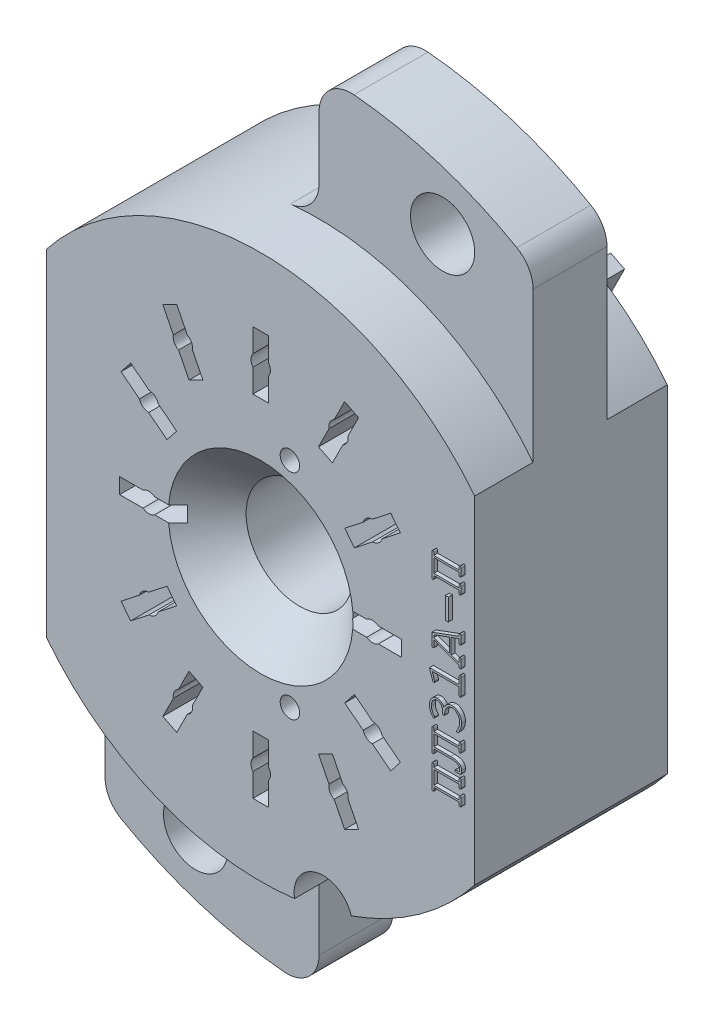
SolidWorks part; units mm, degrees
ref_plane "Front Plane" through (0, 0, 0) normal (0, 0, 1) x (1, 0, 0)
ref_plane "Top Plane" through (0, 0, 0) normal (0, 1, 0) x (1, 0, 0)
ref_plane "Right Plane" through (0, 0, 0) normal (1, 0, 0) x (0, 0, -1)
sketch "Sketch2" plane through (0, 0, 0) normal (0, 0, 1) x (1, 0, 0)
  line L0 (-31.5495, -8.6603) -> (-31.5495, -17.2988)
  line L2 (-31.5495, 8.6603) -> (-31.5495, -8.6603)
  line L4 (-9.5495, 8.6603) -> (-9.5495, -8.6603)
  line L5 (-20.5495, -20.5) -> (-20.5495, -14)
  line L6 (-9.5495, 8.6603) -> (-9.5495, 17.2988)
  line L7 (-20.5495, 14) -> (-20.5495, 20.5)
  arc A0 (-20.5495, -14) -> (-9.5495, -8.6603) centre (-20.5495, 0) ccw
  arc A1 (-20.5495, 14) -> (-31.5495, 8.6603) centre (-20.5495, 0) ccw
  arc A2 (-31.5495, -17.2988) -> (-20.5495, -20.5) centre (-20.5495, 0) ccw
  arc A4 (-9.5495, 17.2988) -> (-20.5495, 20.5) centre (-20.5495, 0) ccw
  arc A6 (-31.5495, -17.2988) -> (-20.5495, -20.5) centre (-20.5495, 0) ccw
  point P9 (-31.5495, -8.6603)
  point P10 (-31.5495, -17.2988)
  point P11 (-20.5495, -20.5)
  dimension "D1" = 28
  dimension "D3" = 41
  dimension "D6" = 11
  dimension "D2" = 22
  dimension "D4" = 17.3205
  dimension "D5" = 11
  dimension "D7" = 8.6386
extrude "Boss-Extrude1" add sketch "Sketch2" along normal blind 3.8 contours L6 A4 L7 A1 L2 L0 A2 L5 A0 L4 region at (-20.5495, 0, 0)
sketch "Sketch3" plane through (0, 0, 0) normal (0, 0, 1) x (1, 0, 0)
  line L0 (-31.5495, -8.6603) -> (-31.5495, -17.2988)
  line L2 (-31.5495, 8.6603) -> (-31.5495, -8.6603)
  line L4 (-9.5495, 8.6603) -> (-9.5495, -8.6603)
  line L5 (-20.5495, -20.5) -> (-20.5495, -14)
  line L6 (-9.5495, 8.6603) -> (-9.5495, 17.2988)
  line L7 (-20.5495, 14) -> (-20.5495, 20.5)
  arc A0 (-20.5495, -14) -> (-9.5495, -8.6603) centre (-20.5495, 0) ccw
  arc A1 (-20.5495, 14) -> (-31.5495, 8.6603) centre (-20.5495, 0) ccw
  arc A2 (-31.5495, -17.2988) -> (-20.5495, -20.5) centre (-20.5495, 0) ccw
  arc A4 (-9.5495, 17.2988) -> (-20.5495, 20.5) centre (-20.5495, 0) ccw
  arc A6 (-31.5495, -17.2988) -> (-20.5495, -20.5) centre (-20.5495, 0) ccw
  point P9 (-31.5495, -8.6603)
  point P10 (-31.5495, -17.2988)
  point P11 (-20.5495, -20.5)
  dimension "D1" = 28
  dimension "D3" = 41
  dimension "D6" = 11
  dimension "D2" = 22
  dimension "D4" = 17.3205
  dimension "D5" = 11
  dimension "D7" = 8.6386
sketch "Sketch4" plane through (0, 0, 3.8) normal (0, 0, 1) x (1, 0, 0)
  line L0 (-9.5495, 8.6603) -> (-9.5495, -8.6603)
  line L1 (-31.5495, -8.6603) -> (-31.5495, 8.6603)
  arc A0 (-9.5495, 8.6603) -> (-31.5495, 8.6603) centre (-20.5495, 0) ccw
  arc A1 (-31.5495, -8.6603) -> (-9.5495, -8.6603) centre (-20.5495, 0) ccw
extrude "Boss-Extrude2" add sketch "Sketch4" along normal blind 3
sketch "Sketch5" plane through (0, 0, 0) normal (0, 0, -1) x (-1, 0, 0)
  line L0 (31.5495, 8.6603) -> (31.5495, -8.6603)
  line L1 (9.5495, 8.6603) -> (9.5495, -8.6603)
  arc A0 (31.5495, 8.6603) -> (9.5495, 8.6603) centre (20.5495, 0) ccw
  arc A1 (9.5495, -8.6603) -> (31.5495, -8.6603) centre (20.5495, 0) ccw
extrude "Boss-Extrude3" add sketch "Sketch5" along normal blind 3.1
sketch "Sketch6" plane through (0, 0, 3.8) normal (0, 0, 1) x (1, 0, 0)
  line L0 (-9.5495, 8.6603) -> (-9.5495, 17.2988) construction
  circle A0 centre (-14.1995, 16.5) radius 1.65
  dimension "D1" = 3.3
  dimension "D2" = 4.65
  dimension "D3" = 2.5
extrude "Cut-Extrude1" cut sketch "Sketch6" against normal up to surface (3.8 mm away) up to face at (-14.8391, 15.6269, 0)
sketch "Sketch12" plane through (0, 0, 0) normal (0, 1, 0) x (1, 0, 0)
  line L0 (-20.5495, -6.8) -> (-20.5495, 3.1) construction
  line L1 (-31.5495, -6.8) -> (-9.5495, -6.8) construction
  line L2 (-9.5495, 3.1) -> (-31.5495, 3.1) construction
pattern_circular "CirPattern1" count 2 every 180 about axis through (-20.5495, 0, 6.8) along (0, 0, -1) of "Cut-Extrude1"
sketch "Sketch13" plane through (0, 0, 6.8) normal (0, 0, 1) x (1, 0, 0)
  line L0 (-19.0495, 5.5) -> (-19.0495, -5.5) construction
  line L1 (-20.5495, 9) -> (-20.5495, -9) construction
  line L2 (-16.5495, 8) -> (-16.5495, -8) construction
  line L3 (-14.7995, 4.5) -> (-14.7995, -4.5) construction
  line L4 (-20.5495, 0) -> (-16.5495, 8) construction
  line L5 (-20.5495, 0) -> (-14.7995, 4.5) construction
  line L6 (-20.5495, 0) -> (-14.7995, 0) construction
  line L7 (-16.2365, 9.5205) -> (-16.7732, 8.4472)
  line L8 (-20.9495, 10.5) -> (-20.1495, 10.5)
  line L9 (-20.9495, 10.5) -> (-20.9495, 9.3)
  line L10 (-20.9495, 7.5) -> (-20.1495, 7.5)
  line L11 (-20.1495, 10.5) -> (-20.1495, 9.3)
  line L14 (-16.2365, 9.5205) -> (-15.521, 9.1628)
  line L15 (-17.5781, 6.8372) -> (-16.8626, 6.4795)
  line L16 (-15.521, 9.1628) -> (-16.0576, 8.0894)
  line L17 (-16.2365, 9.5205) -> (-16.6504, 7.5103) construction
  line L18 (-17.5781, 6.8372) -> (-15.521, 9.1628) construction
  line L19 (-13.3718, 5.1095) -> (-14.3168, 4.3699)
  line L20 (-13.3718, 5.1095) -> (-13.8648, 5.7395)
  line L21 (-15.7343, 3.2605) -> (-16.2273, 3.8905)
  line L22 (-13.8648, 5.7395) -> (-14.8098, 4.9999)
  line L23 (-13.3718, 5.1095) -> (-16.2273, 3.8905) construction
  line L24 (-15.7343, 3.2605) -> (-13.8648, 5.7395) construction
  line L25 (-16.2995, -0.4) -> (-15.0995, -0.4)
  line L26 (-16.2995, -0.4) -> (-16.2995, 0.4)
  line L27 (-13.2995, -0.4) -> (-13.2995, 0.4)
  line L28 (-16.2995, 0.4) -> (-15.0995, 0.4)
  line L29 (-16.2995, -0.4) -> (-13.2995, 0.4) construction
  line L30 (-13.2995, -0.4) -> (-16.2995, 0.4) construction
  line L31 (-20.9495, 8.7) -> (-20.9495, 7.5)
  line L32 (-20.1495, 8.7) -> (-20.1495, 7.5)
  line L33 (-16.3259, 7.5528) -> (-16.8626, 6.4795)
  line L34 (-17.0415, 7.9106) -> (-17.5781, 6.8372)
  line L35 (-15.2823, 4.6301) -> (-16.2273, 3.8905)
  line L36 (-14.7893, 4.0001) -> (-15.7343, 3.2605)
  line L37 (-14.4995, 0.4) -> (-13.2995, 0.4)
  line L38 (-14.4995, -0.4) -> (-13.2995, -0.4)
  line L39 (-20.9495, -10.5) -> (-20.9495, -9.3)
  line L40 (-20.9495, -8.7) -> (-20.9495, -7.5)
  line L41 (-20.9495, -7.5) -> (-20.1495, -7.5)
  line L42 (-20.1495, -8.7) -> (-20.1495, -7.5)
  line L43 (-20.1495, -10.5) -> (-20.1495, -9.3)
  line L44 (-20.9495, -10.5) -> (-20.1495, -10.5)
  line L45 (-16.2365, -9.5205) -> (-15.521, -9.1628)
  line L46 (-15.521, -9.1628) -> (-16.0576, -8.0894)
  line L47 (-16.3259, -7.5528) -> (-16.8626, -6.4795)
  line L48 (-17.5781, -6.8372) -> (-16.8626, -6.4795)
  line L49 (-17.0415, -7.9106) -> (-17.5781, -6.8372)
  line L50 (-16.2365, -9.5205) -> (-16.7732, -8.4472)
  line L51 (-14.7893, -4.0001) -> (-15.7343, -3.2605)
  line L52 (-15.7343, -3.2605) -> (-16.2273, -3.8905)
  line L53 (-15.2823, -4.6301) -> (-16.2273, -3.8905)
  line L54 (-13.8648, -5.7395) -> (-14.8098, -4.9999)
  line L55 (-13.3718, -5.1095) -> (-13.8648, -5.7395)
  line L56 (-13.3718, -5.1095) -> (-14.3168, -4.3699)
  line L57 (-24.8626, -9.5205) -> (-24.3259, -8.4472)
  line L58 (-24.0576, -7.9106) -> (-23.521, -6.8372)
  line L59 (-23.521, -6.8372) -> (-24.2365, -6.4795)
  line L60 (-24.7732, -7.5528) -> (-24.2365, -6.4795)
  line L61 (-25.5781, -9.1628) -> (-25.0415, -8.0894)
  line L62 (-24.8626, -9.5205) -> (-25.5781, -9.1628)
  line L63 (-27.7273, -5.1095) -> (-26.7823, -4.3699)
  line L64 (-27.7273, -5.1095) -> (-27.2343, -5.7395)
  line L65 (-27.2343, -5.7395) -> (-26.2893, -4.9999)
  line L66 (-25.8168, -4.6301) -> (-24.8718, -3.8905)
  line L67 (-25.3648, -3.2605) -> (-24.8718, -3.8905)
  line L68 (-26.3098, -4.0001) -> (-25.3648, -3.2605)
  line L69 (-24.7995, -0.4) -> (-24.7995, 0.4)
  line L70 (-24.7995, 0.4) -> (-25.9995, 0.4)
  line L71 (-26.5995, 0.4) -> (-27.7995, 0.4)
  line L72 (-27.7995, -0.4) -> (-27.7995, 0.4)
  line L73 (-26.5995, -0.4) -> (-27.7995, -0.4)
  line L74 (-24.7995, -0.4) -> (-25.9995, -0.4)
  line L75 (-26.3098, 4.0001) -> (-25.3648, 3.2605)
  line L76 (-25.3648, 3.2605) -> (-24.8718, 3.8905)
  line L77 (-25.8168, 4.6301) -> (-24.8718, 3.8905)
  line L78 (-27.2343, 5.7395) -> (-26.2893, 4.9999)
  line L79 (-27.7273, 5.1095) -> (-27.2343, 5.7395)
  line L80 (-27.7273, 5.1095) -> (-26.7823, 4.3699)
  line L81 (-24.8626, 9.5205) -> (-25.5781, 9.1628)
  line L82 (-25.5781, 9.1628) -> (-25.0415, 8.0894)
  line L83 (-24.7732, 7.5528) -> (-24.2365, 6.4795)
  line L84 (-23.521, 6.8372) -> (-24.2365, 6.4795)
  line L85 (-24.0576, 7.9106) -> (-23.521, 6.8372)
  line L86 (-24.8626, 9.5205) -> (-24.3259, 8.4472)
  circle A0 centre (-20.5495, 0) radius 2.75
  circle A1 centre (-19.0495, 5.5) radius 0.5
  circle A2 centre (-19.0495, -5.5) radius 0.5
  arc A3 (-20.9495, 9.3) -> (-20.9495, 8.7) centre (-20.5495, 9) ccw
  arc A4 (-16.7732, 8.4472) -> (-17.0415, 7.9106) centre (-16.5495, 8) ccw
  arc A5 (-14.8098, 4.9999) -> (-15.2823, 4.6301) centre (-14.7995, 4.5) ccw
  arc A6 (-14.4995, 0.4) -> (-15.0995, 0.4) centre (-14.7995, 0) ccw
  arc A15 (-16.3259, 7.5528) -> (-16.0576, 8.0894) centre (-16.5495, 8) ccw
  arc A16 (-20.1495, 8.7) -> (-20.1495, 9.3) centre (-20.5495, 9) ccw
  arc A17 (-14.7893, 4.0001) -> (-14.3168, 4.3699) centre (-14.7995, 4.5) ccw
  arc A18 (-15.0995, -0.4) -> (-14.4995, -0.4) centre (-14.7995, 0) ccw
  arc A19 (-20.9495, -9.3) -> (-20.9495, -8.7) centre (-20.5495, -9) cw
  arc A20 (-20.1495, -8.7) -> (-20.1495, -9.3) centre (-20.5495, -9) cw
  arc A21 (-16.3259, -7.5528) -> (-16.0576, -8.0894) centre (-16.5495, -8) cw
  arc A22 (-16.7732, -8.4472) -> (-17.0415, -7.9106) centre (-16.5495, -8) cw
  arc A23 (-14.8098, -4.9999) -> (-15.2823, -4.6301) centre (-14.7995, -4.5) cw
  arc A24 (-14.7893, -4.0001) -> (-14.3168, -4.3699) centre (-14.7995, -4.5) cw
  arc A25 (-24.3259, -8.4472) -> (-24.0576, -7.9106) centre (-24.5495, -8) ccw
  arc A26 (-24.7732, -7.5528) -> (-25.0415, -8.0894) centre (-24.5495, -8) ccw
  arc A27 (-26.3098, -4.0001) -> (-26.7823, -4.3699) centre (-26.2995, -4.5) ccw
  arc A28 (-26.2893, -4.9999) -> (-25.8168, -4.6301) centre (-26.2995, -4.5) ccw
  arc A29 (-26.5995, 0.4) -> (-25.9995, 0.4) centre (-26.2995, 0) cw
  arc A30 (-25.9995, -0.4) -> (-26.5995, -0.4) centre (-26.2995, 0) cw
  arc A31 (-26.2893, 4.9999) -> (-25.8168, 4.6301) centre (-26.2995, 4.5) cw
  arc A32 (-26.3098, 4.0001) -> (-26.7823, 4.3699) centre (-26.2995, 4.5) cw
  arc A33 (-24.7732, 7.5528) -> (-25.0415, 8.0894) centre (-24.5495, 8) cw
  arc A34 (-24.3259, 8.4472) -> (-24.0576, 7.9106) centre (-24.5495, 8) cw
  point P7 (-19.0495, 0)
  point P26 (-20.5495, 0)
  point P27 (-16.5495, 0)
  point P28 (-14.7995, 0)
  dimension "D1" = 5.5
  dimension "D2" = 1
  dimension "D5" = 1
  dimension "D11" = 0.8
  dimension "D3" = 5.5
  dimension "D4" = 1.5
  dimension "D6" = 5.75
  dimension "D7" = 18
  dimension "D8" = 16
  dimension "D9" = 9
  dimension "D10" = 4
  dimension "D12" = 3
  dimension "D13" = 1.2
extrude "Cut-Extrude2" cut sketch "Sketch13" against normal up to surface (9.9 mm away) up to face at (-20.5495, 0, -3.1)
sketch "Sketch14" plane through (0, 0, 6.8) normal (0, 0, 1) x (1, 0, 0)
  line L0 (-20.5495, 0) -> (-20.5495, -13.0412) construction
  line L1 (-20.5495, 0) -> (-15.1022, -10.8946) construction
  line L2 (-20.5495, -9.6587) -> (-16.2301, -8.639) construction
  line L3 (-20.5495, 0) -> (-16.7012, -16.3019) construction
  line L4 (-16.2365, -9.5205) -> (-15.521, -9.1628) construction
  line L5 (-20.9495, -10.5) -> (-20.1495, -10.5) construction
  circle A0 centre (-17.333, -13.6255) radius 1.5
  arc A1 (-20.5495, -14) -> (-9.5495, -8.6603) centre (-20.5495, 0) ccw construction
  circle A2 centre (-20.5495, 0) radius 9.6587 construction
  point P10 (-20.5495, -9.6587)
  point P11 (-16.2301, -8.639)
  point P14 (-20.5495, -10.5)
  point P16 (-17.333, -13.6255)
  point P18 (-15.8787, -9.3416)
  point P23 (-20.5495, -10.5)
  dimension "D1" = 3
extrude "Cut-Extrude3" cut sketch "Sketch14" against normal blind 3
chamfer "Chamfer1" distance 2 angle 45 1 edges at (-17.7995, 0, 6.8)
fillet "Fillet1" radius 1.65 6 edges at (-31.5495, -17.2988, 1.9) (-20.5495, -20.5, 1.9) (-20.5495, -14, 1.9) (-20.5495, 14, 1.9) (-20.5495, 20.5, 1.9) (-9.5495, 17.2988, 1.9)
sketch "Sketch15" plane through (0, 0, -3.1) normal (0, 0, -1) x (-1, 0, 0)
  line L0 (24.639, 9.0733) -> (23.7446, 7.2845)
  line L1 (20.1495, 10) -> (20.9495, 10)
  line L2 (20.1495, 10) -> (20.1495, 8)
  line L3 (20.1495, 8) -> (20.9495, 8)
  line L4 (20.9495, 10) -> (20.9495, 8)
  line L5 (24.639, 9.0733) -> (25.3545, 8.7155)
  line L6 (20.1495, 9.3) -> (20.1495, 10.5) construction
  line L7 (20.9495, 10.5) -> (20.9495, 9.3) construction
  line L8 (20.9495, 10.5) -> (20.9495, 7.5) construction
  line L9 (23.7446, 7.2845) -> (24.4601, 6.9267)
  line L10 (25.3545, 8.7155) -> (24.4601, 6.9267)
  line L11 (24.3259, 8.4472) -> (24.8626, 9.5205) construction
  line L12 (23.521, 6.8372) -> (24.0576, 7.9106) construction
  line L13 (26.8405, 5.4313) -> (25.2655, 4.1987)
  line L14 (24.7732, 7.5528) -> (24.2365, 6.4795) construction
  line L15 (24.8626, 9.5205) -> (23.521, 6.8372) construction
  line L16 (26.8405, 5.4313) -> (27.3336, 4.8013)
  line L17 (25.2655, 4.1987) -> (25.7586, 3.5687)
  line L18 (27.3336, 4.8013) -> (25.7586, 3.5687)
  line L19 (26.2893, 4.9999) -> (27.2343, 5.7395) construction
  line L20 (24.8718, 3.8905) -> (25.8168, 4.6301) construction
  line L21 (27.7995, 0.4) -> (24.7995, 0.4) construction
  line L22 (27.7273, 5.1095) -> (26.7823, 4.3699) construction
  line L23 (24.8718, 3.8905) -> (27.2343, 5.7395) construction
  line L24 (27.2995, 0.4) -> (25.2995, 0.4)
  line L25 (27.2995, 0.4) -> (27.2995, -0.4)
  line L26 (25.2995, 0.4) -> (25.2995, -0.4)
  line L27 (27.2995, -0.4) -> (25.2995, -0.4)
  line L28 (26.5995, 0.4) -> (27.7995, 0.4) construction
  line L29 (24.7995, 0.4) -> (25.9995, 0.4) construction
  line L30 (20.5495, 0) -> (20.5495, 9) construction
  line L31 (27.7995, -0.4) -> (26.5995, -0.4) construction
  line L32 (20.5495, 0) -> (24.5495, 8) construction
  line L33 (20.5495, 0) -> (26.2995, 4.5) construction
  line L34 (20.5495, 0) -> (26.2995, 0) construction
  line L35 (25.2655, -4.1987) -> (25.7586, -3.5687)
  line L36 (27.3336, -4.8013) -> (25.7586, -3.5687)
  line L37 (26.8405, -5.4313) -> (27.3336, -4.8013)
  line L38 (26.8405, -5.4313) -> (25.2655, -4.1987)
  line L39 (23.7446, -7.2845) -> (24.4601, -6.9267)
  line L40 (25.3545, -8.7155) -> (24.4601, -6.9267)
  line L41 (24.639, -9.0733) -> (25.3545, -8.7155)
  line L42 (24.639, -9.0733) -> (23.7446, -7.2845)
  line L43 (20.1495, -8) -> (20.9495, -8)
  line L44 (20.9495, -10) -> (20.9495, -8)
  line L45 (20.1495, -10) -> (20.9495, -10)
  line L46 (20.1495, -10) -> (20.1495, -8)
  line L47 (16.4601, -9.0733) -> (17.3545, -7.2845)
  line L48 (16.4601, -9.0733) -> (15.7446, -8.7155)
  line L49 (15.7446, -8.7155) -> (16.639, -6.9267)
  line L50 (17.3545, -7.2845) -> (16.639, -6.9267)
  line L51 (14.2586, -5.4313) -> (15.8336, -4.1987)
  line L52 (14.2586, -5.4313) -> (13.7655, -4.8013)
  line L53 (13.7655, -4.8013) -> (15.3405, -3.5687)
  line L54 (15.8336, -4.1987) -> (15.3405, -3.5687)
  line L55 (15.7995, 0.4) -> (15.7995, -0.4)
  line L56 (13.7995, -0.4) -> (15.7995, -0.4)
  line L57 (13.7995, 0.4) -> (13.7995, -0.4)
  line L58 (13.7995, 0.4) -> (15.7995, 0.4)
  line L59 (15.8336, 4.1987) -> (15.3405, 3.5687)
  line L60 (13.7655, 4.8013) -> (15.3405, 3.5687)
  line L61 (14.2586, 5.4313) -> (13.7655, 4.8013)
  line L62 (14.2586, 5.4313) -> (15.8336, 4.1987)
  line L63 (17.3545, 7.2845) -> (16.639, 6.9267)
  line L64 (15.7446, 8.7155) -> (16.639, 6.9267)
  line L65 (16.4601, 9.0733) -> (15.7446, 8.7155)
  line L66 (16.4601, 9.0733) -> (17.3545, 7.2845)
  point P8 (20.9495, 9)
  point P13 (20.9495, 9)
  point P28 (24.1918, 8.1789)
  point P29 (24.1918, 8.1789)
  point P44 (26.053, 4.815)
  point P45 (26.053, 4.815)
  point P60 (26.2995, 0.4)
  point P61 (26.2995, 0.4)
  dimension "D1" = 2
extrude "Boss-Extrude4" add sketch "Sketch15" along normal blind 4 separate body
sketch "Sketch16" plane through (0, 0, 6.8) normal (0, 0, 1) x (1, 0, 0)
  line L0 (-10.0495, -9.2601) -> (-10.0495, 9.2601) construction
  line L1 (-9.5495, -8.6603) -> (-9.5495, 8.6603) construction
  arc A0 (-15.8937, -13.2031) -> (-9.5495, -8.6603) centre (-20.5495, 0) ccw construction
  arc A2 (-9.5495, 8.6603) -> (-22.0256, 13.922) centre (-20.5495, 0) ccw construction
  text T0 "ПЛ31А-П" font "Courier New" height 1.5
  dimension "D1" = 0.5
extrude "Boss-Extrude5" add sketch "Sketch16" along normal blind 0.2
